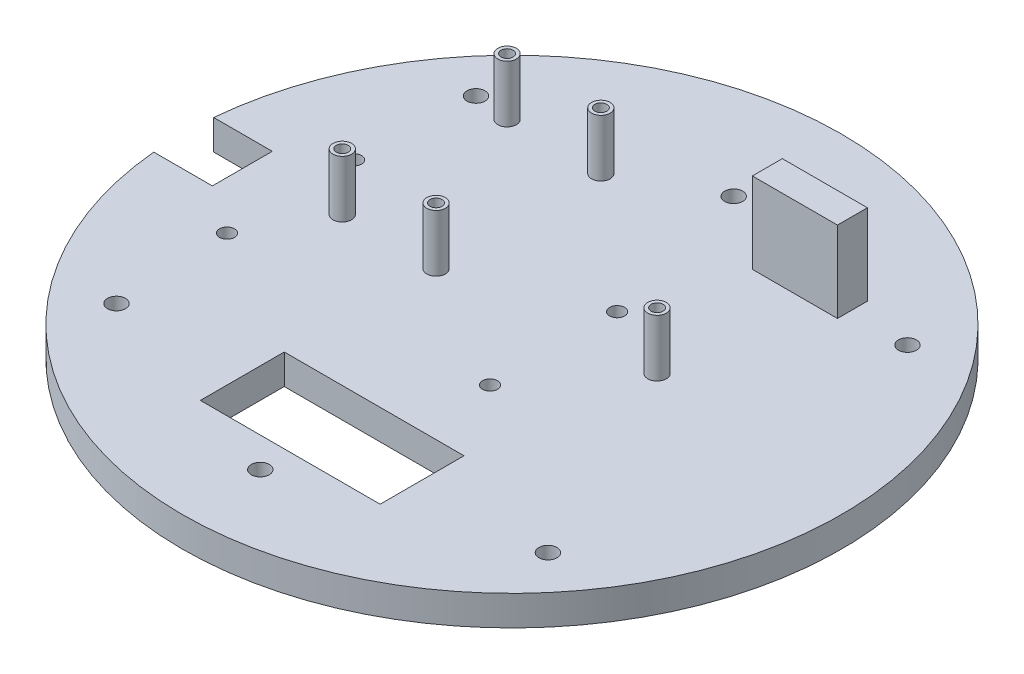
SolidWorks part; units mm, degrees
ref_plane "Front Plane" through (0, 0, 0) normal (0, 0, 1) x (1, 0, 0)
ref_plane "Top Plane" through (0, 0, 0) normal (0, 1, 0) x (1, 0, 0)
ref_plane "Right Plane" through (0, 0, 0) normal (1, 0, 0) x (0, 0, -1)
sketch "Sketch2" plane through (0, 0, 0) normal (0, 1, 0) x (1, 0, 0)
  line L0 (0, 0) -> (9.1621, 0) construction
  line L1 (0, 0) -> (0, 13.2968) construction
  line L3 (-15, -23) -> (15, -23)
  line L4 (-15, -23) -> (-15, -37)
  line L5 (-15, -37) -> (15, -37)
  line L6 (15, -23) -> (15, -37)
  line L7 (-15, -23) -> (15, -37) construction
  line L8 (-15, -37) -> (15, -23) construction
  circle A0 centre (0, 0) radius 55
  point P5 (0, -30)
  point P12 (0, 0)
  dimension "D1" = 110
  dimension "D2" = 14
  dimension "D3" = 30
  dimension "D4" = 30
extrude "Boss-Extrude1" add sketch "Sketch2" along normal blind 5
sketch "Sketch3" plane through (0, 0, 0) normal (0, -1, 0) x (1, 0, 0)
  line L0 (-15, 0) -> (-15, 12.9052) construction
  line L5 (0, 0) -> (14.6599, 0) construction
  circle A0 centre (-36.95, 10.6) radius 2.5 construction
  circle A4 centre (-36.95, -10.6) radius 2.5 construction
  circle A5 centre (6.95, -10.6) radius 2.5 construction
  circle A6 centre (6.95, 10.6) radius 2.5 construction
  point P0 (0, 0)
  dimension "D3" = 5
  dimension "D1" = 10.6
  dimension "D2" = 21.95
  dimension "D10" = 15
sketch "Sketch15" plane through (0, 5, 0) normal (0, 1, 0) x (1, 0, 0)
  line L0 (-22.2011, 29.3371) -> (-22.2011, 35.4897) construction
  line L7 (-21.0891, 15.4599) -> (-18.0632, 15.4599) construction
  circle A0 centre (-30.0261, 29.2099) radius 1.55
  circle A1 centre (-14.3761, 29.2099) radius 1.55
  circle A2 centre (-14.3761, 1.7099) radius 1.55
  circle A3 centre (-30.0261, 1.7099) radius 1.55
  dimension "D3" = 3.1
  dimension "D6" = 7.825
  dimension "D5" = 15.4599
  dimension "D7" = 13.75
  dimension "D1" = 13.75
  dimension "D2" = 22.2011
  dimension "D4" = 7.825
extrude "Boss-Extrude3" add sketch "Sketch15" along normal blind 9.5
hole_wizard "Ø2.0mm Dowel Hole1" positions "3DSketch10" profile "Sketch16" hole size "Ø2.0" standard "DIN"
sketch3d "3DSketch10"
  line L0 (-30.0261, 14.5, -29.2099) -> (-30.0261, 5, -29.2099) construction
  line L1 (-30.0261, 14.5, -1.7099) -> (-30.0261, 5, -1.7099) construction
  line L2 (-14.3761, 14.5, -1.7099) -> (-14.3761, 5, -1.7099) construction
  line L3 (-14.3761, 14.5, -29.2099) -> (-14.3761, 5, -29.2099) construction
  point P0 (-30.0261, 14.5, -29.2099)
  point P4 (-30.0261, 14.5, -1.7099)
  point P8 (-14.3761, 14.5, -1.7099)
  point P12 (-14.3761, 14.5, -29.2099)
sketch "Sketch16" plane through (-30.0261, 14.5, -29.2099) normal (1, 0, 0) x (0, 0, 1)
  line L0 (0, 0) -> (0, 10.7509)
  line L1 (0, 10.7509) -> (1, 10.15)
  line L2 (1, 10.15) -> (1, 0)
  line L5 (1, 0) -> (0, 0)
  line L10 (0, 10.7509) -> (-1, 10.15) construction
  line L11 (0, -6.35) -> (0, 107.95) construction
  dimension "Hole Dia." = 2
  dimension "Hole Depth" = 10.15
  dimension "Drill Angle" = 118
sketch "Sketch17" plane through (0, 5, 0) normal (0, 1, 0) x (1, 0, 0)
  line L1 (12.1174, 33) -> (26.3174, 33)
  line L2 (12.1174, 33) -> (12.1174, 28)
  line L3 (12.1174, 28) -> (26.3174, 28)
  line L4 (26.3174, 33) -> (26.3174, 28)
  line L5 (12.1174, 33) -> (26.3174, 28) construction
  line L6 (12.1174, 28) -> (26.3174, 33) construction
  circle A0 centre (19.2174, 5) radius 1.55
  point P2 (19.2174, 30.5)
  dimension "D1" = 3.1
  dimension "D2" = 5
  dimension "D3" = 19.2174
  dimension "D4" = 23
  dimension "D5" = 14.2
  dimension "D6" = 5
extrude "Boss-Extrude4" add sketch "Sketch17" along normal blind 9.5
hole_wizard "Ø2.0mm Dowel Hole2" positions "3DSketch11" profile "Sketch18" hole size "Ø2.0" standard "DIN"
sketch3d "3DSketch11"
  line L0 (19.2174, 14.5, -5) -> (19.2174, 5, -5) construction
  point P0 (19.2174, 14.5, -5)
sketch "Sketch18" plane through (19.2174, 14.5, -5) normal (1, 0, 0) x (0, 0, 1)
  line L0 (0, 0) -> (0, 10.7509)
  line L1 (0, 10.7509) -> (1, 10.15)
  line L2 (1, 10.15) -> (1, 0)
  line L5 (1, 0) -> (0, 0)
  line L10 (0, 10.7509) -> (-1, 10.15) construction
  line L11 (0, -6.35) -> (0, 107.95) construction
  dimension "Hole Dia." = 2
  dimension "Hole Depth" = 10.15
  dimension "Drill Angle" = 118
sketch "Sketch19" plane through (0, 14.5, 0) normal (0, 1, 0) x (1, 0, 0)
  line L0 (26.3174, 28) -> (26.3174, 33) construction
  line L1 (12.1174, 28) -> (26.3174, 28) construction
  line L2 (12.1174, 33) -> (12.1174, 28) construction
  line L3 (26.3174, 33) -> (12.1174, 33) construction
  line L4 (26.3174, 28) -> (26.3174, 33)
  line L5 (12.1174, 28) -> (26.3174, 28)
  line L6 (12.1174, 33) -> (12.1174, 28)
  line L7 (26.3174, 33) -> (12.1174, 33)
extrude "Boss-Extrude5" add sketch "Sketch19" along normal blind 4
sketch "Sketch21" plane through (0, 5, 0) normal (0, 1, 0) x (1, 0, 0)
  line L8 (0, 0) -> (25.1353, 0) construction
  line L13 (25.1353, 0) -> (0, 0) construction
  line L14 (0, 0) -> (0, 20.9244) construction
  line L15 (-45, 5) -> (-45, -5)
  line L16 (-45, 5) -> (-55, 5)
  line L17 (-45, -5) -> (-55, -5)
  line L18 (-55, 5) -> (-55, -5)
  circle A2 centre (0, 0) radius 55 construction
  point P10 (-45, 0)
  dimension "D1" = 10
  dimension "D2" = 10
  dimension "D3" = 0
extrude "Cut-Extrude1" cut sketch "Sketch21" against normal through all
sketch "Sketch30" plane through (0, 0, 0) normal (0, -1, 0) x (1, 0, 0)
  line L0 (0, 0) -> (0, 26.3182) construction
  line L1 (0, 0) -> (19.571, 0) construction
  circle A0 centre (-36, 30) radius 3 construction
  circle A1 centre (36, 30) radius 3 construction
  circle A2 centre (36, -30) radius 3 construction
  circle A3 centre (-36, -30) radius 3 construction
  dimension "D1" = 6
  dimension "D2" = 36
  dimension "D3" = 30
hole_wizard "Ø3.0mm Dowel Hole6" positions "3DSketch18" profile "Sketch35" hole size "Ø3.0" standard "DIN" end condition through all
sketch3d "3DSketch18"
  point P0 (0, 0, 42)
  point P2 (0, 0, -37)
  dimension "D1" = 42
  dimension "D3" = 37
sketch "Sketch35" plane through (0, 0, 42) normal (1, 0, 0) x (0, 0, -1)
  line L0 (0, 0) -> (0, 18.5)
  line L1 (0, 18.5) -> (1.5, 18.5)
  line L2 (1.5, 18.5) -> (1.5, 0)
  line L5 (1.5, 0) -> (0, 0)
  line L11 (0, -6.35) -> (0, 107.95) construction
  dimension "Thru Hole Dia." = 3
  dimension "Thru Hole Depth" = 18.5
hole_wizard "Ø3.0mm Dowel Hole7" positions "3DSketch19" profile "Sketch36" hole size "Ø3.0" standard "DIN" end condition through all
sketch3d "3DSketch19"
  point P0 (-36, 0, 30)
  point P3 (36, 0, 30)
  point P6 (36, 0, -30)
  point P9 (-36, 0, -30)
sketch "Sketch36" plane through (-36, 0, 30) normal (1, 0, 0) x (0, 0, -1)
  line L0 (0, 0) -> (0, 18.5)
  line L1 (0, 18.5) -> (1.5, 18.5)
  line L2 (1.5, 18.5) -> (1.5, 0)
  line L5 (1.5, 0) -> (0, 0)
  line L11 (0, -6.35) -> (0, 107.95) construction
  dimension "Thru Hole Dia." = 3
  dimension "Thru Hole Depth" = 18.5
hole_wizard "Ø2.5mm Dowel Hole1" positions "3DSketch20" profile "Sketch37" hole size "Ø2.5" standard "DIN" end condition through all
sketch3d "3DSketch20"
  point P0 (-36.95, 0, 10.6)
  point P3 (6.95, 0, 10.6)
  point P6 (6.95, 0, -10.6)
  point P9 (-36.95, 0, -10.6)
sketch "Sketch37" plane through (-36.95, 0, 10.6) normal (1, 0, 0) x (0, 0, -1)
  line L0 (0, 0) -> (0, 18.5)
  line L1 (0, 18.5) -> (1.25, 18.5)
  line L2 (1.25, 18.5) -> (1.25, 0)
  line L5 (1.25, 0) -> (0, 0)
  line L11 (0, -6.35) -> (0, 107.95) construction
  dimension "Thru Hole Dia." = 2.5
  dimension "Thru Hole Depth" = 18.5
